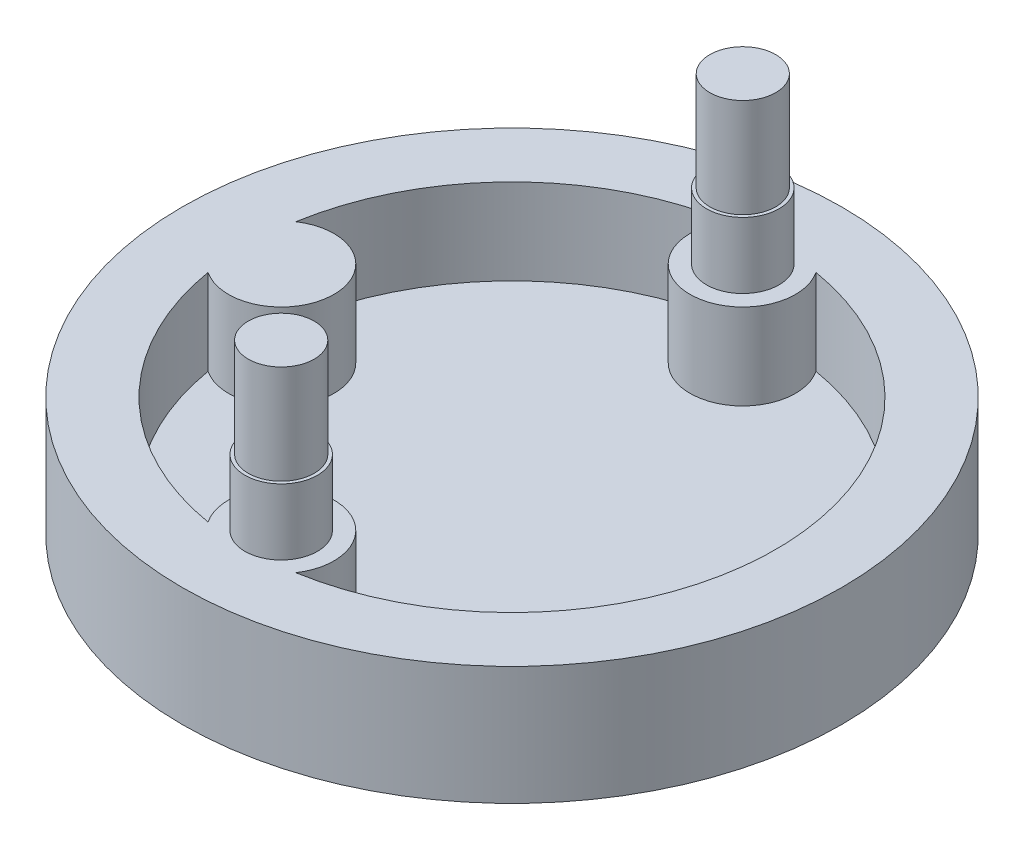
SolidWorks part; units mm, degrees
ref_plane "Front Plane" through (0, 0, 0) normal (0, 0, 1) x (1, 0, 0)
ref_plane "Top Plane" through (0, 0, 0) normal (0, 1, 0) x (1, 0, 0)
ref_plane "Right Plane" through (0, 0, 0) normal (1, 0, 0) x (0, 0, -1)
sketch "Sketch1" plane through (0, 0, 0) normal (0, 1, 0) x (1, 0, 0)
  circle A0 centre (0, 0) radius 50
  circle A1 centre (0, 0) radius 40
extrude "Boss-Extrude1" add sketch "Sketch1" along normal blind 18 contours A0
extrude "Cut-Extrude1" cut sketch "Sketch1<3>" along normal blind 13 from offset 5 contours A1
sketch "Sketch1<3>" plane through (0, 0, 0) normal (0, 1, 0) x (1, 0, 0) same geometry as "Sketch1"
sketch "Sketch2" plane through (0, 18, 0) normal (0, 1, 0) x (1, 0, 0)
  circle A0 centre (0, 0) radius 35 construction
  circle A1 centre (0, 35) radius 8
  circle A2 centre (35, 0) radius 8 [skipped]
  circle A3 centre (0, -35) radius 8
  circle A4 centre (-35, 0) radius 8
  point P5 (0, 0)
  point P6 (0, 0)
  point P14 (0, 0)
  dimension "D1" = 4
extrude "Boss-Extrude2" add sketch "Sketch2" against normal up to next
sketch "Sketch3" plane through (0, 18, 0) normal (0, 1, 0) x (1, 0, 0)
  circle A0 centre (0, 35) radius 5.5
  circle A1 centre (0, -35) radius 5.5
extrude "Boss-Extrude3" add sketch "Sketch3" along normal blind 10
sketch "Sketch4" plane through (0, 28, 0) normal (0, 1, 0) x (1, 0, 0)
  circle A0 centre (0, -35) radius 5
  circle A1 centre (0, 35) radius 5
  circle A2 centre (0, 35) radius 5.5 construction
extrude "Boss-Extrude4" add sketch "Sketch4" along normal blind 15
sketch "Sketch5" plane through (0, 0, 0) normal (0, -1, 0) x (1, 0, 0)
  circle A0 centre (0, 35) radius 4
  circle A1 centre (0, -35) radius 4
  circle A2 centre (-35, 0) radius 4
extrude "Cut-Extrude2" cut sketch "Sketch5" against normal blind 18 contours A0 | A1 region at (0, 0, 35) region at (0, 0, -35)
extrude "Cut-Extrude3" cut sketch "Sketch5<3>" against normal blind 8 contours A2 region at (-35, 0, 0)
sketch "Sketch5<3>" plane through (0, 0, 0) normal (0, -1, 0) x (1, 0, 0) same geometry as "Sketch5"
